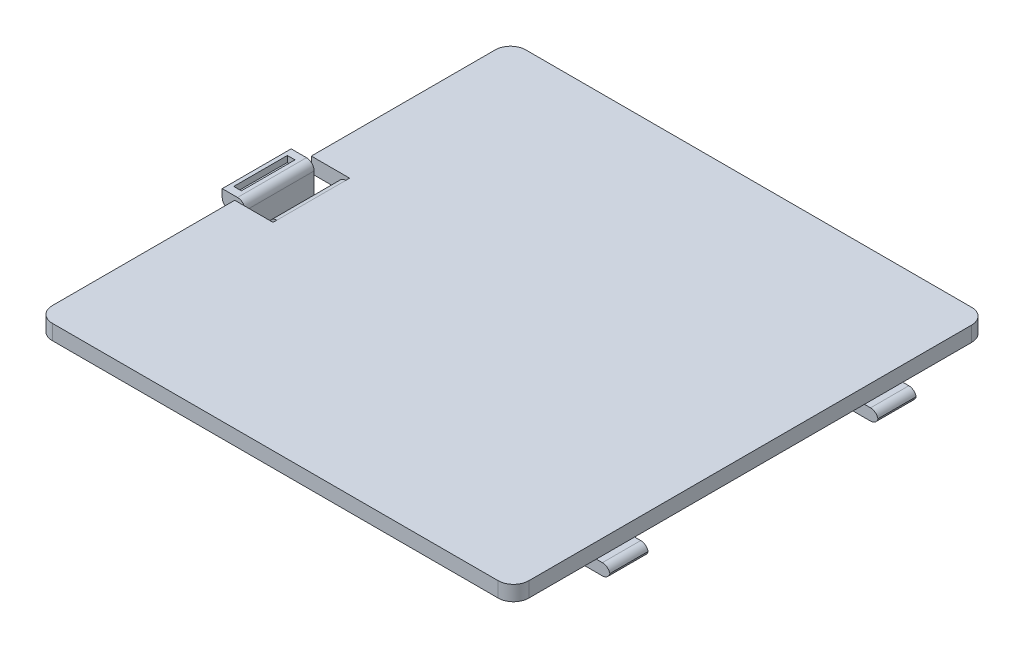
SolidWorks part; units mm, degrees
ref_plane "Front Plane" through (0, 0, 0) normal (0, 0, 1) x (1, 0, 0)
ref_plane "Top Plane" through (0, 0, 0) normal (0, 1, 0) x (1, 0, 0)
ref_plane "Right Plane" through (0, 0, 0) normal (1, 0, 0) x (0, 0, -1)
sketch "Sketch2" plane through (0, 0, 0) normal (0, 1, 0) x (1, 0, 0)
  line L0 (-98.1098, -87.5101) -> (49.7302, -87.5101)
  line L1 (-103.1898, -82.4301) -> (-103.1898, 64.4099)
  line L2 (-98.1098, 69.4899) -> (49.7302, 69.4899)
  line L3 (54.8102, -82.4301) -> (54.8102, 64.4099)
  arc A0 (-98.1098, -87.5101) -> (-103.1898, -82.4301) centre (-98.1098, -82.4301) cw
  arc A1 (49.7302, -87.5101) -> (54.8102, -82.4301) centre (49.7302, -82.4301) ccw
  arc A2 (49.7302, 69.4899) -> (54.8102, 64.4099) centre (49.7302, 64.4099) cw
  arc A3 (-103.1898, 64.4099) -> (-98.1098, 69.4899) centre (-98.1098, 64.4099) cw
  point P10 (54.8102, 69.4899)
  point P13 (-103.1898, 69.4899)
  dimension "D2" = 5.08
  dimension "D1" = 158
  dimension "D3" = 157
extrude "Boss-Extrude1" add sketch "Sketch2" along normal blind 5
sketch "Sketch8" plane through (0, 5, 0) normal (0, 1, 0) x (1, 0, 0)
  line L0 (-103.1898, 64.4099) -> (-103.1898, -82.4301) construction
  line L1 (-103.1898, 3.4499) -> (-90.4898, 3.4499)
  line L2 (-103.1898, 3.4499) -> (-103.1898, -21.9501)
  line L3 (-103.1898, -21.9501) -> (-90.4898, -21.9501)
  line L4 (-90.4898, 3.4499) -> (-90.4898, -21.9501)
  line L5 (49.7302, 69.4899) -> (-98.1098, 69.4899) construction
  dimension "D1" = 25.4
  dimension "D2" = 12.7
  dimension "D3" = 66.04
extrude "Cut-Extrude1" cut sketch "Sketch8" against normal blind 12.7
sketch "Sketch9" plane through (0, 0, 21.9501) normal (0, 0, -1) x (-1, 0, 0)
  line L0 (90.4898, 5) -> (90.4898, -9.5101)
  line L1 (93.0298, -12.0501) -> (100.9847, -12.0501)
  line L2 (103.5247, -9.5101) -> (103.5247, 5)
  line L3 (103.5247, 5) -> (100.9847, 5)
  line L4 (93.0298, 5) -> (93.0298, -3.471)
  line L5 (97.0073, -9.5101) -> (98.4447, -9.5101)
  line L6 (100.9847, -6.9701) -> (100.9847, 5)
  line L7 (93.0298, 5) -> (90.4898, 5)
  arc A0 (90.4898, -9.5101) -> (93.0298, -12.0501) centre (93.0298, -9.5101) ccw
  arc A1 (100.9847, -12.0501) -> (103.5247, -9.5101) centre (100.9847, -9.5101) ccw
  arc A2 (98.4447, -9.5101) -> (100.9847, -6.9701) centre (98.4447, -6.9701) ccw
  spline S0 degree 2 poles (93.0298, -3.471) (93.1813, -7.7564) (97.0073, -9.5101) knots 0 0 0 1 1 1
  dimension "D4" = 2.54
  dimension "D1" = 2.54
  dimension "D2" = 2.54
  dimension "D3" = 2.54
  dimension "D5" = 17.0501
extrude "Boss-Extrude6" add sketch "Sketch9" along normal blind 22.86 from offset 1.27
fillet "Fillet3" radius 2.54 1 edges at (-90.4898, 0, 9.2501)
sketch "Sketch12" plane through (-103.5247, 0, 0) normal (-1, 0, 0) x (0, 0, 1)
  line L0 (20.6801, 5) -> (20.6801, 0) construction
  line L1 (-2.1799, 5) -> (20.6801, 5)
  line L2 (-2.1799, 5) -> (-2.1799, -0.08)
  line L3 (-2.1799, -0.08) -> (20.6801, -0.08)
  line L4 (20.6801, 5) -> (20.6801, -0.08)
  dimension "D1" = 5.08
extrude "Boss-Extrude7" add sketch "Sketch12" along normal blind 5.08
fillet "Fillet8" radius 2.54 1 edges at (-100.9847, 5, 9.2501)
sketch "Sketch13" plane through (0, 5, 0) normal (0, 1, 0) x (1, 0, 0)
  line L0 (-108.6047, 2.1799) -> (-103.5247, 2.1799) construction
  line L1 (-104.7947, -0.3601) -> (-107.3347, -0.3601)
  line L2 (-104.7947, -0.3601) -> (-104.7947, -18.1401)
  line L3 (-104.7947, -18.1401) -> (-107.3347, -18.1401)
  line L4 (-107.3347, -0.3601) -> (-107.3347, -18.1401)
  line L5 (-108.6047, -20.6801) -> (-103.5247, -20.6801) construction
  line L6 (-103.5247, -20.6801) -> (-103.5247, 2.1799) construction
  line L8 (-108.6047, -20.6801) -> (-108.6047, 2.1799) construction
  dimension "D1" = 2.54
  dimension "D2" = 2.54
  dimension "D3" = 1.27
  dimension "D4" = 1.27
extrude "Cut-Extrude2" cut sketch "Sketch13" against normal blind 2.032
sketch "Sketch14" plane through (0, 0, -2.1799) normal (0, 0, -1) x (-1, 0, 0)
  line L0 (103.5247, -4.5768) -> (105.0487, -4.5768)
  line L1 (103.5247, -9.5101) -> (103.5247, -0.08) construction
  line L2 (105.0487, -4.5768) -> (103.5247, -7.3708)
  line L3 (103.5247, -7.3708) -> (103.5247, -4.5768)
  dimension "D1" = 1.524
  dimension "D2" = 2.794
extrude "Boss-Extrude8" add sketch "Sketch14" against normal up to surface (22.86 mm away) up to face at (-97.6502, -3.1315, 20.6801)
fillet "Fillet5" radius 2.54 1 edges at (-93.0298, 5, 9.2501)
fillet "Fillet6" radius 2.54 1 edges at (-108.6047, -0.08, 9.2501)
sketch "Sketch15" plane through (0, 0, -69.4899) normal (0, 0, -1) x (-1, 0, 0)
  line L4 (-85.2178, 2.5) -> (-23.3625, 2.5) construction
  line L6 (-59.3702, 0) -> (-49.2102, 0)
  line L7 (-59.3702, -3.81) -> (-59.3702, 0)
  line L8 (-49.2102, -3.81) -> (-59.3702, -3.81)
  line L9 (-49.2102, 0) -> (-49.2102, -3.81)
  point P8 (-54.2902, 2.5)
extrude "Boss-Extrude9" add sketch "Sketch15" against normal blind 12.7 from offset 27.94 offset against normal yes
extrude "Boss-Extrude10" add sketch "Sketch15<2>" against normal blind 12.7 from offset 116.84 offset against normal yes
sketch "Sketch15<2>" plane through (0, 0, -69.4899) normal (0, 0, -1) x (-1, 0, 0) same geometry as "Sketch15"
fillet "Fillet7" radius 2.54 6 edges at (59.3702, 0, 53.7001) (59.3702, -3.81, 53.7001) (49.2102, 0, 53.7001) (59.3702, -3.81, -35.1999) (59.3702, 0, -35.1999) (49.2102, 0, -35.1999)
